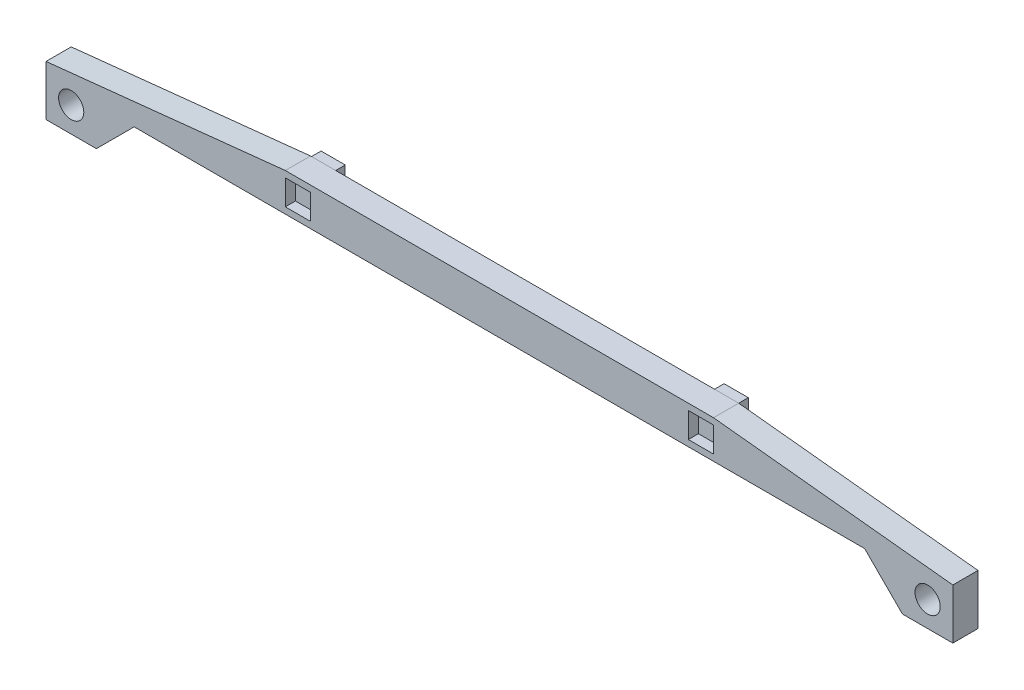
SolidWorks part; units mm, degrees
ref_plane "Front Plane" through (0, 0, 0) normal (0, 0, 1) x (1, 0, 0)
ref_plane "Top Plane" through (0, 0, 0) normal (0, 1, 0) x (1, 0, 0)
ref_plane "Right Plane" through (0, 0, 0) normal (1, 0, 0) x (0, 0, -1)
sketch "Sketch2" plane through (0, 0, 0) normal (0, 0, 1) x (1, 0, 0)
  line L0 (-85, 0) -> (85, 0) construction
  line L1 (-90, -5) -> (90, -5)
  line L2 (-90, -5) -> (-90, 5)
  line L3 (-90, 5) -> (90, 5)
  line L4 (90, -5) -> (90, 5)
  line L5 (-90, -5) -> (90, 5) construction
  line L6 (-90, 5) -> (90, -5) construction
  circle A0 centre (-85, 0) radius 2.5
  circle A1 centre (85, 0) radius 2.5
  point P0 (0, 0)
  point P15 (0, 0)
  dimension "D1" = 5
  dimension "D2" = 170
  dimension "D3" = 180
  dimension "D4" = 10
extrude "Boss-Extrude1" add sketch "Sketch2" along normal mid plane 5
sketch "Sketch3" plane through (0, 0, 2.5) normal (0, 0, 1) x (1, 0, 0)
  line L0 (-40, 7.5) -> (40, 7.5) construction
  line L1 (-42.5, 5) -> (-37.5, 5)
  line L2 (-42.5, 5) -> (-42.5, 10)
  line L3 (-42.5, 10) -> (-37.5, 10)
  line L4 (-37.5, 5) -> (-37.5, 10)
  line L5 (-42.5, 5) -> (-37.5, 10) construction
  line L6 (-42.5, 10) -> (-37.5, 5) construction
  line L7 (37.5, 5) -> (42.5, 5)
  line L8 (37.5, 5) -> (37.5, 10)
  line L9 (37.5, 10) -> (42.5, 10)
  line L10 (42.5, 5) -> (42.5, 10)
  line L11 (37.5, 5) -> (42.5, 10) construction
  line L12 (37.5, 10) -> (42.5, 5) construction
  line L14 (90, 5) -> (-90, 5) construction
  point P0 (-40, 7.5)
  point P5 (40, 7.5)
  point P12 (0, 7.5)
  line M2 (90, 5) -> (-90, 5)
  dimension "D1" = 80
  dimension "D2" = 5
extrude "Boss-Extrude2" add sketch "Sketch3" against normal blind 7 contours L10 L9 L8 M2 | L2 L1 L4 L3 | L8 L7 L10 L9 region at (40, 7.5, 2.5)
chamfer "Chamfer1" distance 5 angle 45 4 edges at (-37.5, 5, 0) (-42.5, 5, 0) (37.5, 5, 0) (42.5, 5, 0)
sketch "Sketch4" plane through (0, 0, -4.5) normal (0, 0, -1) x (-1, 0, 0)
  line L0 (42.5, 10) -> (37.5, 10) construction
  line L1 (37.5, 10) -> (37.5, 5) construction
  line L2 (37.5, 5) -> (42.5, 5) construction
  line L3 (42.5, 5) -> (42.5, 10) construction
  line L5 (-37.5, 5) -> (-37.5, 10) construction
  line L6 (-37.5, 10) -> (-42.5, 10) construction
  line L7 (-42.5, 10) -> (-42.5, 5) construction
  line L8 (42.5, 10) -> (37.5, 10)
  line L9 (37.5, 10) -> (37.5, 5)
  line L10 (37.5, 5) -> (42.5, 5)
  line L11 (42.5, 5) -> (42.5, 10)
  line L12 (-42.5, 5) -> (-37.5, 5)
  line L13 (-37.5, 5) -> (-37.5, 10)
  line L14 (-37.5, 10) -> (-42.5, 10)
  line L15 (-42.5, 10) -> (-42.5, 5)
  line L16 (42.4, 9.9) -> (37.6, 9.9)
  line L17 (37.6, 9.9) -> (37.6, 5.1)
  line L18 (37.6, 5.1) -> (42.4, 5.1)
  line L19 (42.4, 5.1) -> (42.4, 9.9)
  line L20 (-42.4, 5.1) -> (-37.6, 5.1)
  line L21 (-37.6, 5.1) -> (-37.6, 9.9)
  line L22 (-37.6, 9.9) -> (-42.4, 9.9)
  line L23 (-42.4, 9.9) -> (-42.4, 5.1)
  line L24 (-42.5, 5) -> (-37.5, 5) construction
  line M9 (-42.5, 5) -> (-37.5, 5)
  line M10 (-37.5, 5) -> (-37.5, 10)
  line M11 (-37.5, 10) -> (-42.5, 10)
  line M12 (-42.5, 10) -> (-42.5, 5)
  dimension "D1" = 0.1
extrude "Cut-Extrude1" cut sketch "Sketch4" against normal up to surface (2 mm away) contours L10 L11 L8 L9 L19 L18 L17 L16 | L23 L22 L21 L20 M12 M9 M10 M11 region at (-42.4293, 7.5, -4.5) region at (42.4293, 7.5, -4.5) up to face at (-82.5, 0, -2.5)
sketch "Sketch5" plane through (0, 0, 2.5) normal (0, 0, 1) x (1, 0, 0)
  line L0 (-80, -5) -> (-72.5, 2.5)
  line L1 (-90, -5) -> (90, -5) construction
  line L2 (-72.5, 2.5) -> (72.5, 2.5)
  line L3 (72.5, 2.5) -> (80, -5)
  line L4 (-80, -5) -> (80, -5)
  line L6 (-85, 0) -> (-85, -5) construction
  circle A0 centre (-85, 0) radius 2.5 construction
  circle A1 centre (-85, 0) radius 2.5 construction
  point P4 (0, 2.5)
  dimension "D1" = 5
  dimension "D2" = 45
  dimension "D3" = 7.5
extrude "Cut-Extrude2" cut sketch "Sketch5" against normal through all
sketch "Sketch6" plane through (0, 0, 2.5) normal (0, 0, 1) x (1, 0, 0)
  line L0 (-42.5, 10) -> (-90, 5)
  line L1 (-90, 5) -> (-47.5, 5)
  line L2 (-47.5, 5) -> (-42.5, 10)
  line L3 (42.5, 10) -> (47.5, 5)
  line L4 (47.5, 5) -> (90, 5)
  line L5 (90, 5) -> (42.5, 10)
extrude "Boss-Extrude3" add sketch "Sketch6" against normal up to surface (5 mm away) up to face at (0, 3.4375, -2.5)
sketch "Sketch7" plane through (0, 0, 2.5) normal (0, 0, 1) x (1, 0, 0)
  line L0 (-37.5, 10) -> (37.5, 10)
  line L1 (37.5, 10) -> (32.5, 5)
  line L2 (32.5, 5) -> (-32.5, 5)
  line L3 (-32.5, 5) -> (-37.5, 10)
extrude "Boss-Extrude4" add sketch "Sketch7" against normal up to surface (5 mm away) up to face at (0, 3.2143, -2.5)
sketch "Sketch8" plane through (0, 0, 2.5) normal (0, 0, 1) x (1, 0, 0)
  line L0 (0, 2.5) -> (0, 10) construction
  line L1 (-42.5, 3.75) -> (-37.5, 3.75)
  line L2 (-42.5, 3.75) -> (-42.5, 8.75)
  line L3 (-42.5, 8.75) -> (-37.5, 8.75)
  line L4 (-37.5, 3.75) -> (-37.5, 8.75)
  line L5 (-42.5, 3.75) -> (-37.5, 8.75) construction
  line L6 (-42.5, 8.75) -> (-37.5, 3.75) construction
  line L7 (37.5, 3.75) -> (42.5, 3.75)
  line L8 (37.5, 3.75) -> (37.5, 8.75)
  line L9 (37.5, 8.75) -> (42.5, 8.75)
  line L10 (42.5, 3.75) -> (42.5, 8.75)
  line L11 (37.5, 3.75) -> (42.5, 8.75) construction
  line L12 (37.5, 8.75) -> (42.5, 3.75) construction
  line L13 (0, 6.25) -> (40, 6.25) construction
  line L14 (72.5, 2.5) -> (-72.5, 2.5) construction
  line L15 (-42.5, 10) -> (42.5, 10) construction
  line L16 (0, 10) -> (0, 6.25) construction
  line L17 (0, 6.25) -> (-40, 6.25) construction
  point P0 (-39.2892, 6.9608)
  point P5 (41.9953, 8.2453)
  point P15 (-39.8045, 6.25)
  point P16 (40, 6.25)
  point P19 (-40, 6.25)
  dimension "D1" = 5
  dimension "D2" = 80
extrude "Cut-Extrude3" cut sketch "Sketch8" against normal blind 2
